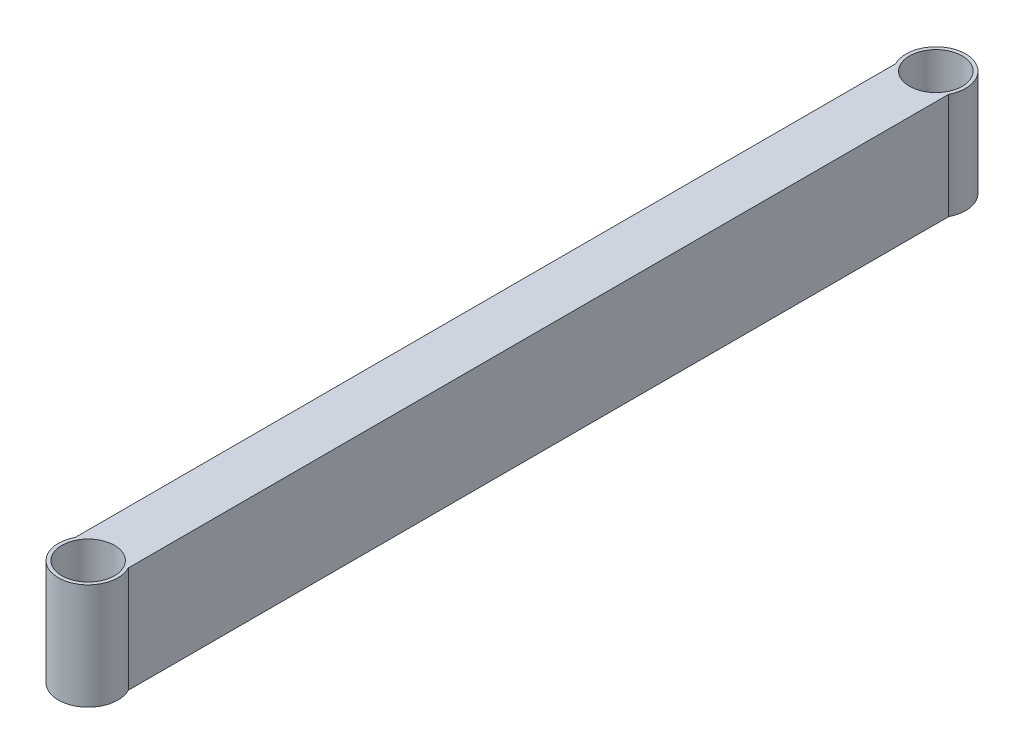
SolidWorks part; units mm, degrees
material "6061-T6 (SS)"
ref_plane "Front Plane" through (0, 0, 0) normal (0, 0, 1) x (1, 0, 0)
ref_plane "Top Plane" through (0, 0, 0) normal (0, 1, 0) x (1, 0, 0)
ref_plane "Right Plane" through (0, 0, 0) normal (1, 0, 0) x (0, 0, -1)
sketch "Sketch1" plane through (0, 0, 0) normal (0, 0, 1) x (1, 0, 0)
  line L0 (-11.1252, -23.8252) -> (-11.1252, 23.8252)
  line L1 (-12.7, -25.4) -> (12.7, -25.4)
  line L2 (-12.7, -25.4) -> (-12.7, 25.4)
  line L3 (-12.7, 25.4) -> (12.7, 25.4)
  line L4 (12.7, -25.4) -> (12.7, 25.4)
  line L5 (-12.7, -25.4) -> (12.7, 25.4) construction
  line L6 (-12.7, 25.4) -> (12.7, -25.4) construction
  line L7 (-11.1252, 23.8252) -> (11.1252, 23.8252)
  line L8 (11.1252, -23.8252) -> (11.1252, 23.8252)
  line L9 (-11.1252, -23.8252) -> (11.1252, -23.8252)
  point P0 (0, 0)
  dimension "D1" = 25.4
  dimension "D2" = 50.8
  dimension "D3" = 1.5748
extrude "Boss-Extrude1" add sketch "Sketch1" along normal blind 406.4
sketch "Sketch2" plane through (0, 25.4, 0) normal (0, 1, 0) x (1, 0, 0)
  line L0 (12.7, -406.4) -> (-12.7, -406.4) construction
  circle A0 centre (0, 0) radius 14.2875
  circle A1 centre (0, -406.4) radius 14.2875
  dimension "D1" = 28.575
  dimension "D2" = 28.575
extrude "Cut-Extrude1" cut sketch "Sketch2" against normal through all
sketch "Sketch3" plane through (0, 25.4, 0) normal (0, 1, 0) x (1, 0, 0)
  line L0 (-12.7, -397.4197) -> (-11.1125, -397.4197) construction
  line L1 (-12.7, -399.8546) -> (-12.7, -6.5454) construction
  line L2 (-12.7, -8.9803) -> (-11.1125, -8.9803) construction
  line L3 (-12.7, -399.8546) -> (-12.7, -6.5454) construction
  circle A0 centre (0, 0) radius 14.2875
  circle A1 centre (0, -406.4) radius 14.2875
  circle A2 centre (0, -406.4) radius 12.6365
  circle A3 centre (0, 0) radius 12.6365
  dimension "D1" = 1.651
  dimension "D3" = 25.273
  dimension "D5" = 25.273
  dimension "D4" = 1.5875
  dimension "D6" = 1.5875
  dimension "D7" = 388.4395
  dimension "D2" = 1.651
extrude "Boss-Extrude2" add sketch "Sketch3" against normal blind 50.8
sketch "Sketch4" plane through (12.7, 0, 0) normal (1, 0, 0) x (0, 0, -1)
  line L0 (-63.6954, 0) -> (-44.6454, 0) construction
  line L1 (-63.6954, 4.826) -> (-44.6454, 4.826)
  line L2 (-63.6954, -4.826) -> (-44.6454, -4.826)
  line L3 (-399.8546, -25.4) -> (-6.5454, -25.4) construction
  line L6 (-6.5454, -25.4) -> (-6.5454, 25.4) construction
  line L8 (-361.7546, 0) -> (-342.7046, 0) construction
  line L9 (-361.7546, 4.826) -> (-342.7046, 4.826)
  line L10 (-361.7546, -4.826) -> (-342.7046, -4.826)
  line L11 (-399.8546, 25.4) -> (-399.8546, -25.4) construction
  arc A0 (-63.6954, 4.826) -> (-63.6954, -4.826) centre (-63.6954, 0) ccw
  arc A1 (-44.6454, -4.826) -> (-44.6454, 4.826) centre (-44.6454, 0) ccw
  arc A4 (-361.7546, 4.826) -> (-361.7546, -4.826) centre (-361.7546, 0) ccw
  arc A5 (-342.7046, -4.826) -> (-342.7046, 4.826) centre (-342.7046, 0) ccw
  point P3 (-54.1704, 0)
  point P17 (-6.5454, 0)
  point P20 (-352.2296, 0)
  dimension "D3" = 9.652
  dimension "D1" = 38.1
  dimension "D2" = 19.05
  dimension "D4" = 9.652
  dimension "D5" = 25.4
  dimension "D6" = 38.1
  dimension "D7" = 19.05
extrude "Cut-Extrude2" [suppressed] cut sketch "Sketch4" against normal up to next
sketch "Sketch5" plane through (0, 25.4, 0) normal (0, 1, 0) x (1, 0, 0)
  line L0 (0, 0) -> (0, -406.4) construction
  line L2 (12.7, -39.6875) -> (15.0813, -39.6875)
  line L3 (12.7, -39.6875) -> (12.7, -58.7375)
  line L4 (12.7, -58.7375) -> (15.0813, -58.7375)
  line L5 (15.0813, -39.6875) -> (15.0813, -58.7375)
  line L9 (0, -203.2) -> (60.9307, -203.2) construction
  line L10 (-12.7, -366.7125) -> (-15.0812, -366.7125) construction
  line L11 (-12.7, -366.7125) -> (-12.7, -347.6625) construction
  line L12 (-12.7, -347.6625) -> (-15.0812, -347.6625) construction
  line L13 (-15.0812, -366.7125) -> (-15.0812, -347.6625) construction
  point P10 (-13.8906, -366.7125)
  dimension "D1" = 12.7
  dimension "D2" = 39.6875
  dimension "D3" = 19.05
  dimension "D4" = 2.3813
  dimension "D7" = 19.05
  dimension "D8" = 39.6875
  dimension "D5" = 2.3812
  dimension "D6" = 12.7
extrude "Boss-Extrude3" [suppressed] add sketch "Sketch5" along normal blind 42.5577 and the other way blind 38.1
sketch "Sketch6" [suppressed] plane through (-12.7, 0, 0) normal (1, 0, 0) x (0, 0, -1)
  line L0 (-361.6325, 47.3202) -> (-352.7425, 47.3202) construction
  line L1 (-361.6325, 49.0982) -> (-352.7425, 49.0982)
  line L2 (-361.6325, 45.5422) -> (-352.7425, 45.5422)
  line L3 (-361.6325, 58.1152) -> (-352.7425, 58.1152) construction
  line L4 (-361.6325, 59.8932) -> (-352.7425, 59.8932)
  line L5 (-361.6325, 56.3372) -> (-352.7425, 56.3372)
  line L6 (-366.7125, 66.3702) -> (-347.6625, 66.3702) construction
  line L7 (-366.7125, 25.4) -> (-366.7125, 66.3702) construction
  line L8 (-347.6625, 25.4) -> (-347.6625, 66.3702) construction
  arc A0 (-361.6325, 49.0982) -> (-361.6325, 45.5422) centre (-361.6325, 47.3202) ccw
  arc A1 (-352.7425, 45.5422) -> (-352.7425, 49.0982) centre (-352.7425, 47.3202) ccw
  arc A2 (-361.6325, 59.8932) -> (-361.6325, 56.3372) centre (-361.6325, 58.1152) ccw
  arc A3 (-352.7425, 56.3372) -> (-352.7425, 59.8932) centre (-352.7425, 58.1152) ccw
  point P2 (-357.1875, 47.3202)
  point P7 (-357.1875, 58.1152)
  dimension "D2" = 1.778
  dimension "D3" = 10.795
  dimension "D6" = 5.08
  dimension "D1" = 19.05
  dimension "D4" = 5.08
  dimension "D5" = 5.08
extrude "Cut-Extrude3" [suppressed] cut sketch "Sketch6" against normal through all
sketch "Sketch7" [suppressed] plane through (15.0813, 0, 0) normal (1, 0, 0) x (0, 0, -1)
  line L0 (-53.6575, 59.8297) -> (-44.7675, 59.8297) construction
  line L1 (-53.6575, 61.6077) -> (-44.7675, 61.6077)
  line L2 (-53.6575, 58.0517) -> (-44.7675, 58.0517)
  line L3 (-44.7675, 48.9077) -> (-53.6575, 48.9077) construction
  line L4 (-44.7675, 47.1297) -> (-53.6575, 47.1297)
  line L5 (-44.7675, 50.6857) -> (-53.6575, 50.6857)
  line L6 (-58.7375, 67.9577) -> (-39.6875, 67.9577) construction
  line L7 (-58.7375, -12.7) -> (-58.7375, 67.9577) construction
  line L8 (-39.6875, -12.7) -> (-39.6875, 67.9577) construction
  arc A0 (-53.6575, 61.6077) -> (-53.6575, 58.0517) centre (-53.6575, 59.8297) ccw
  arc A1 (-44.7675, 58.0517) -> (-44.7675, 61.6077) centre (-44.7675, 59.8297) ccw
  arc A2 (-44.7675, 47.1297) -> (-44.7675, 50.6857) centre (-44.7675, 48.9077) ccw
  arc A3 (-53.6575, 50.6857) -> (-53.6575, 47.1297) centre (-53.6575, 48.9077) ccw
  point P2 (-49.2125, 59.8297)
  point P7 (-49.2125, 48.9077)
  dimension "D2" = 1.778
  dimension "D1" = 19.05
  dimension "D3" = 5.08
  dimension "D4" = 5.08
  dimension "D5" = 10.922
  dimension "D6" = 5.08
extrude "Cut-Extrude4" [suppressed] cut sketch "Sketch7" against normal blind 2.54
chamfer "Chamfer1" [suppressed] distance 1.0668 angle 40
equation "\"D8@Sketch5\"=\"D2@Sketch5\""
equation "\"mount\"=1.5625"
equation "\"D2@Sketch5\"=\"mount\""
